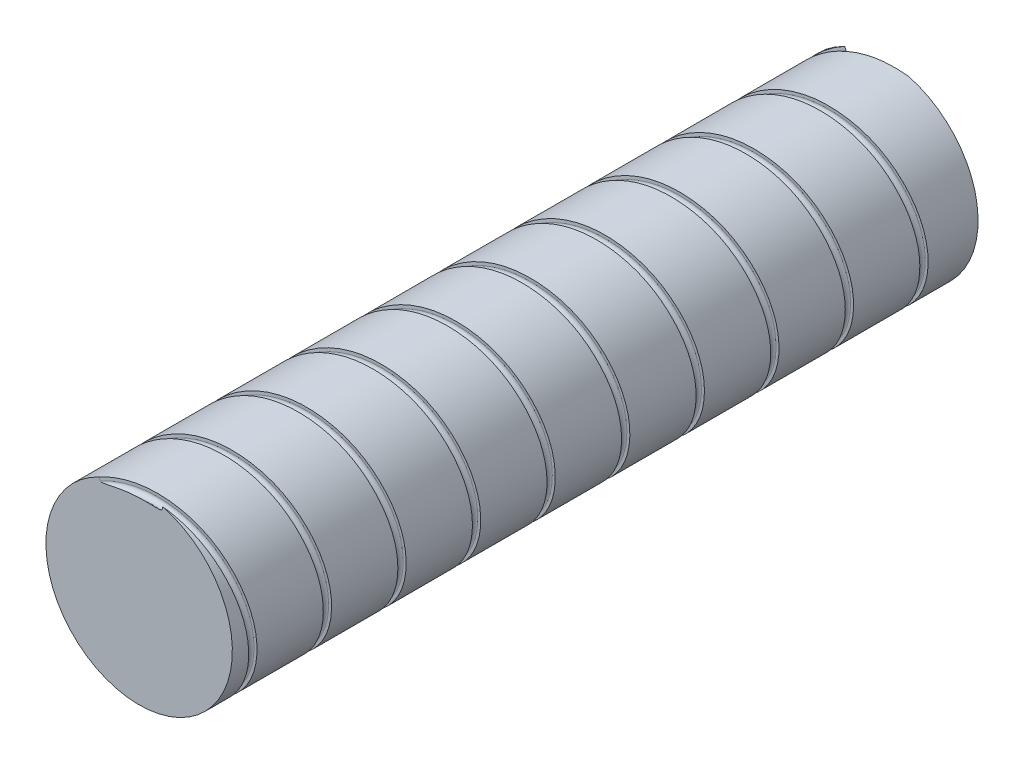
SolidWorks part; units mm, degrees
ref_plane "Front Plane" through (0, 0, 0) normal (0, 0, 1) x (1, 0, 0)
ref_plane "Top Plane" through (0, 0, 0) normal (0, 1, 0) x (1, 0, 0)
ref_plane "Right Plane" through (0, 0, 0) normal (1, 0, 0) x (0, 0, -1)
sketch "Sketch1" plane through (0, 0, 0) normal (0, 0, 1) x (1, 0, 0)
  circle A0 centre (0, 0) radius 2
  dimension "D1" = 4
extrude "Boss-Extrude1" add sketch "Sketch1" along normal blind 16
sketch "Sketch2" plane through (0, 0, 0) normal (0, 0, -1) x (-1, 0, 0)
  circle A0 centre (0, 0) radius 2
  dimension "D1" = 4
curve "Helix/Spiral1" pitch 1.6 height 16 turns 10
sketch "Sketch4" plane through (0, 0, 0) normal (1, 0, 0) x (0, 0, -1)
  line L0 (-15.9754, 1.9349) -> (-15.9754, 2.0687) construction
  line L1 (-16.0645, 1.9349) -> (-16.0645, 2.0687)
  line L2 (-15.8862, 1.9349) -> (-15.8862, 2.0687)
  arc A0 (-16.0645, 1.9349) -> (-15.8862, 1.9349) centre (-15.9754, 1.9349) ccw
  arc A1 (-15.8862, 2.0687) -> (-16.0645, 2.0687) centre (-15.9754, 2.0687) ccw
  point P2 (-15.9754, 2.0018)
sweep "Cut-Sweep2" cut profiles "Sketch4" path "Helix/Spiral1"
